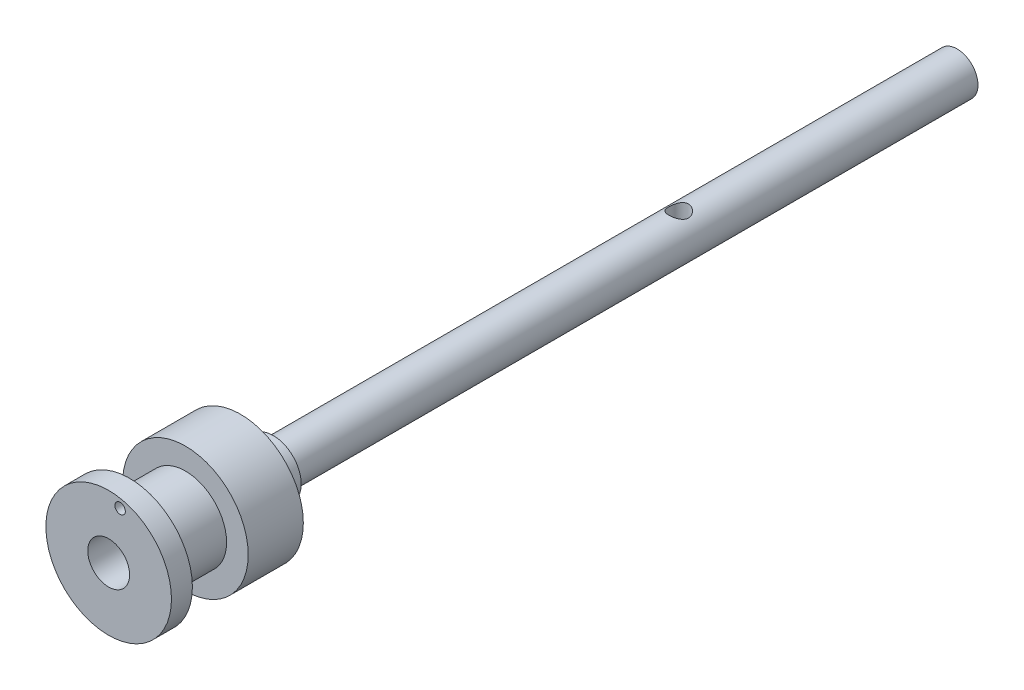
SolidWorks part; units mm, degrees
material "1060 Alloy"
ref_plane "Front Plane" through (0, 0, 0) normal (0, 0, 1) x (1, 0, 0)
ref_plane "Top Plane" through (0, 0, 0) normal (0, 1, 0) x (1, 0, 0)
ref_plane "Right Plane" through (0, 0, 0) normal (1, 0, 0) x (0, 0, -1)
sketch "Sketch1" plane through (0, 0, 0) normal (0, 0, 1) x (1, 0, 0)
  circle A0 centre (0, 0) radius 3
  dimension "D1" = 6
extrude "Boss-Extrude1" add sketch "Sketch1" along normal blind 98
sketch "Sketch2" plane through (0, 0, 98) normal (0, 0, 1) x (1, 0, 0)
  circle A0 centre (0, 0) radius 4
  dimension "D1" = 8
extrude "Boss-Extrude2" add sketch "Sketch2" along normal blind 4.7
sketch "Sketch3" plane through (0, 0, 102.7) normal (0, 0, 1) x (1, 0, 0)
  circle A0 centre (0, 0) radius 9
  dimension "D1" = 18
extrude "Boss-Extrude3" add sketch "Sketch3" along normal blind 7.9
sketch "Sketch4" plane through (0, 0, 110.6) normal (0, 0, 1) x (1, 0, 0)
  circle A0 centre (0, 0) radius 5.9
  dimension "D1" = 11.8
extrude "Boss-Extrude4" add sketch "Sketch4" along normal blind 8
sketch "Sketch5" plane through (0, 0, 118.6) normal (0, 0, 1) x (1, 0, 0)
  circle A0 centre (0, 0) radius 9
  dimension "D1" = 18
extrude "Boss-Extrude5" add sketch "Sketch5" along normal blind 3
sketch "Sketch6" plane through (0, 0, 0) normal (0, 1, 0) x (1, 0, 0)
  line L0 (0, 0) -> (0, -39.9) construction
  circle A0 centre (0, -39.9) radius 1.4
  dimension "D2" = 2.8
  dimension "D1" = 39.9
extrude "Cut-Extrude1" cut sketch "Sketch6" against normal blind 82 and the other way blind 82
sketch "Sketch7" plane through (0, 0, 121.6) normal (0, 0, 1) x (1, 0, 0)
  circle A0 centre (0, 0) radius 3
  circle A1 centre (1.6378, 7.5882) radius 0.75
  dimension "D1" = 6
  dimension "D2" = 1.5
extrude "Cut-Extrude2" cut sketch "Sketch7" against normal blind 9
